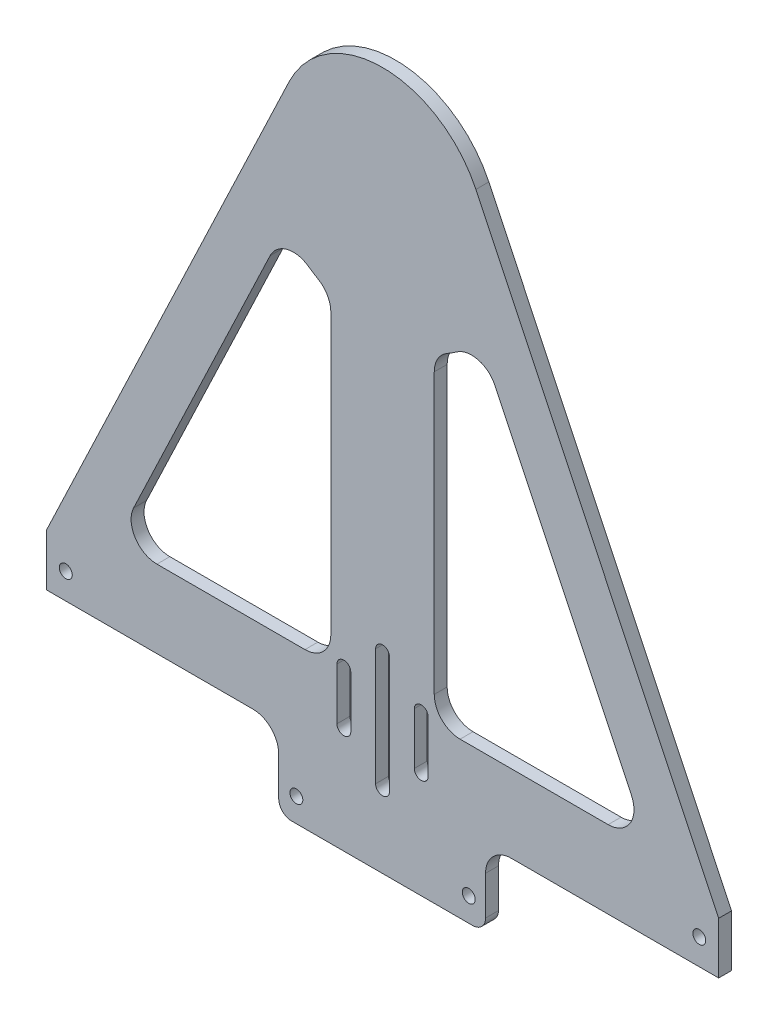
SolidWorks part; units mm, degrees
material "Titanium Ti-8Al-1Mo-1V"
ref_plane "Front Plane" through (0, 0, 0) normal (0, 0, 1) x (1, 0, 0)
ref_plane "Top Plane" through (0, 0, 0) normal (0, 1, 0) x (1, 0, 0)
ref_plane "Right Plane" through (0, 0, 0) normal (1, 0, 0) x (0, 0, -1)
sketch "Sketch1" plane through (0, 0, 0) normal (0, 0, 1) x (1, 0, 0)
  line L0 (0, -58.42) -> (0, 58.42) construction
  line L2 (-82.55, 55.7897) -> (-82.55, -52.07)
  line L3 (-76.2, -58.42) -> (76.2, -58.42)
  line L4 (82.55, 55.7897) -> (82.55, -52.07)
  line L5 (-82.55, 58.42) -> (82.55, -58.42) construction
  line L6 (-82.55, -58.42) -> (82.55, 58.42) construction
  line L7 (-80.6901, 60.2799) -> (-75.4296, 65.5404)
  line L8 (-70.9395, 67.4003) -> (-50.8, 67.4003)
  line L9 (-46.3099, 65.5404) -> (-41.0494, 60.2799)
  line L10 (46.3099, 65.5404) -> (41.0494, 60.2799)
  line L11 (70.9395, 67.4003) -> (50.8, 67.4003)
  line L12 (80.6901, 60.2799) -> (75.4296, 65.5404)
  line L13 (-73.5697, 67.4003) -> (-82.55, 67.4003) construction
  line L14 (-82.55, 67.4003) -> (-82.55, 58.42) construction
  line L15 (-36.5592, 58.42) -> (0, 58.42)
  line L16 (0, 58.42) -> (36.5592, 58.42)
  circle A0 centre (-77.7875, -35.052) radius 1.5875
  circle A1 centre (-77.7875, -11.684) radius 1.5875
  circle A2 centre (-77.7875, 11.684) radius 1.5875
  circle A3 centre (-77.7875, 35.052) radius 1.5875
  circle A4 centre (77.7875, 35.052) radius 1.5875
  circle A5 centre (77.7875, 11.684) radius 1.5875
  circle A6 centre (77.7875, -11.684) radius 1.5875
  circle A7 centre (77.7875, -35.052) radius 1.5875
  arc A8 (82.55, 55.7897) -> (80.6901, 60.2799) centre (76.2, 55.7897) ccw
  arc A9 (75.4296, 65.5404) -> (70.9395, 67.4003) centre (70.9395, 61.0503) ccw
  arc A10 (46.3099, 65.5404) -> (50.8, 67.4003) centre (50.8, 61.0503) cw
  arc A11 (41.0494, 60.2799) -> (36.5592, 58.42) centre (36.5592, 64.77) cw
  arc A12 (-36.5592, 58.42) -> (-41.0494, 60.2799) centre (-36.5592, 64.77) cw
  arc A13 (-46.3099, 65.5404) -> (-50.8, 67.4003) centre (-50.8, 61.0503) ccw
  arc A14 (-70.9395, 67.4003) -> (-75.4296, 65.5404) centre (-70.9395, 61.0503) ccw
  arc A15 (-82.55, 55.7897) -> (-80.6901, 60.2799) centre (-76.2, 55.7897) cw
  arc A16 (76.2, -58.42) -> (82.55, -52.07) centre (76.2, -52.07) ccw
  arc A17 (-76.2, -58.42) -> (-82.55, -52.07) centre (-76.2, -52.07) cw
  circle A18 centre (-70.9395, 61.0503) radius 1.5875
  circle A19 centre (-50.8, 61.0503) radius 1.5875
  circle A20 centre (50.8, 61.0503) radius 1.5875
  circle A21 centre (70.9395, 61.0503) radius 1.5875
  point P0 (0, 0)
  point P36 (73.5697, 67.4003)
  point P39 (48.1697, 67.4003)
  point P42 (39.1895, 58.42)
  point P45 (-39.1895, 58.42)
  point P48 (-48.1697, 67.4003)
  dimension "D3" = 3.175
  dimension "D11" = 6.35
  dimension "D12" = 6.35
  dimension "D13" = 3.175
  dimension "D14" = 3.175
  dimension "D1" = 165.1
  dimension "D2" = 116.84
  dimension "D4" = 23.368
  dimension "D5" = 4.7625
  dimension "D7" = 46.736
  dimension "D8" = 12.7
  dimension "D9" = 135
  dimension "D10" = 25.4
  dimension "D6" = 4
extrude "Boss-Extrude1" [suppressed] add sketch "Sketch1" along normal blind 1.5
sketch "Sketch2" [suppressed] plane through (0, 0, 1.5) normal (0, 0, 1) x (1, 0, 0)
  line L0 (0, -45.72) -> (0, 6.3634) construction
  line L1 (0, -58.42) -> (0, 63.5) construction
  line L3 (-82.55, 1.8599) -> (82.55, 1.8599) construction
  line L4 (-82.55, 55.7897) -> (-82.55, -52.07) construction
  line L5 (82.55, -52.07) -> (82.55, 55.7897) construction
  line L7 (-76.2, -58.42) -> (76.2, -58.42) construction
  circle A0 centre (0, -45.72) radius 1.9062
  circle A1 centre (0, 6.3634) radius 1.9062
  dimension "D2" = 3.8125
  dimension "D3" = 3.8125
  dimension "D1" = 52.0834
  dimension "D4" = 12.7
extrude "Cut-Extrude1" [suppressed] cut sketch "Sketch2" against normal through all
sketch "Sketch3" [suppressed] plane through (0, 0, 1.5) normal (0, 0, 1) x (1, 0, 0)
  line L0 (0, 50.8) -> (0, 30.8) construction
  line L1 (-10, 40.8) -> (10, 40.8) construction
  line L2 (-10, 40.8) -> (0, 50.8) construction
  line L3 (0, 50.8) -> (10, 40.8) construction
  line L4 (10, 40.8) -> (0, 30.8) construction
  line L5 (0, 30.8) -> (-10, 40.8) construction
  line L6 (0, 63.5) -> (0, -58.42) construction
  line L8 (-76.2, -58.42) -> (76.2, -58.42) construction
  circle A0 centre (0, 50.8) radius 1.8669
  circle A1 centre (-10, 40.8) radius 1.8669
  circle A2 centre (0, 30.8) radius 1.8669
  circle A3 centre (10, 40.8) radius 1.8669
  dimension "D1" = 3.7338
  dimension "D2" = 12.7
extrude "Cut-Extrude2" [suppressed] cut sketch "Sketch3" against normal through all
sketch "Sketch4" [suppressed] plane through (0, 0, 1.5) normal (0, 0, 1) x (1, 0, 0)
  line L0 (0, 58.42) -> (0, -58.42) construction
  line L1 (36.5592, 58.42) -> (-36.5592, 58.42) construction
  line L2 (-76.2, -58.42) -> (76.2, -58.42) construction
  line L5 (0, 33.045) -> (0, 52.045) construction
  line L6 (-9.5, 42.545) -> (9.5, 42.545) construction
  circle A14 centre (0, 42.545) radius 8 construction
  circle A15 centre (0, 42.545) radius 9.5 construction
  circle A16 centre (0, 50.545) radius 1.5
  circle A17 centre (0, 34.545) radius 1.5
  circle A18 centre (-9.5, 42.545) radius 1.5
  circle A19 centre (9.5, 42.545) radius 1.5
  dimension "D1" = 15.875
  dimension "D3" = 16
  dimension "D4" = 19
  dimension "D5" = 3
  dimension "D6" = 3
  dimension "D7" = 3
  dimension "D8" = 3
extrude "Cut-Extrude3" [suppressed] cut sketch "Sketch4" against normal through all
sketch "Sketch5" plane through (0, 0, 0) normal (0, 0, 1) x (1, 0, 0)
  line L0 (0, 58.42) -> (0, 26.67) construction
  line L1 (-82.55, 58.42) -> (82.55, 58.42) construction
  line L2 (-82.55, 58.42) -> (-82.55, 45.72)
  line L4 (82.55, 58.42) -> (82.55, 45.72)
  line L5 (82.55, 58.42) -> (22.9335, 183.6386)
  line L8 (77.7875, 45.72) -> (77.7875, 58.42) construction
  line L11 (0, -48.26) -> (0, -46.3538) construction
  line L12 (0, 58.42) -> (0, 172.72) construction
  line L14 (-82.55, 45.72) -> (-31.849, 45.72)
  line L15 (-22.324, 26.67) -> (22.126, 26.67)
  line L16 (-25.499, 29.845) -> (-25.499, 39.37)
  line L17 (25.301, 29.845) -> (25.301, 39.37)
  line L18 (31.651, 45.72) -> (82.55, 45.72)
  line L19 (-82.55, 58.42) -> (-22.9335, 183.6386)
  line L20 (-77.7875, 45.72) -> (-77.7875, 58.42) construction
  line L23 (0, -0.6801) -> (0, 0) construction
  line L24 (0, 26.67) -> (0, 58.42) construction
  line L26 (0, 58.42) -> (-82.55, 58.42) construction
  line L27 (-61.138, 73.8497) -> (-27.6156, 144.2603)
  line L28 (0, -48.26) -> (0, -46.3538) construction
  line L37 (68.4841, 58.42) -> (11.4667, 178.1793) construction
  line L38 (31.651, 58.42) -> (68.4841, 58.42) construction
  line L39 (12.601, 39.37) -> (12.601, 39.37) construction
  line L40 (-12.799, 39.37) -> (12.601, 39.37) construction
  line L41 (-12.799, 39.37) -> (-12.799, 39.37) construction
  line L42 (-68.4841, 58.42) -> (-31.849, 58.42) construction
  line L43 (-12.7, 71.12) -> (-12.7, 139.7244)
  line L44 (-68.4841, 58.42) -> (-11.4667, 178.1793) construction
  line L45 (68.4841, 58.42) -> (68.4841, 58.42) construction
  line L46 (-55.4047, 64.77) -> (-19.05, 64.77)
  line L47 (-12.7, 58.42) -> (-12.7, 172.72) construction
  line L48 (19.05, 64.77) -> (55.4047, 64.77) construction
  line L49 (-82.55, 64.77) -> (82.55, 64.77) construction
  line L50 (-68.4841, 58.42) -> (-68.4841, 58.42) construction
  line L51 (61.138, 73.8497) -> (27.6156, 144.2603)
  line L52 (55.4047, 64.77) -> (19.05, 64.77)
  line L53 (12.7, 71.12) -> (12.7, 139.7244)
  line L54 (-11.2, 52.9151) -> (-11.2, 65.6151)
  line L55 (-7.8, 52.9151) -> (-7.8, 65.6151)
  line L56 (-1.7, 44.9151) -> (-1.7, 73.6151)
  line L57 (1.7, 44.9151) -> (1.7, 73.6151)
  line L58 (7.8, 52.9151) -> (7.8, 65.6151)
  line L59 (11.2, 52.9151) -> (11.2, 65.6151)
  arc A12 (-25.499, 39.37) -> (-31.849, 45.72) centre (-31.849, 39.37) ccw
  arc A13 (25.301, 39.37) -> (31.651, 45.72) centre (31.651, 39.37) cw
  arc A14 (25.301, 29.845) -> (22.126, 26.67) centre (22.126, 29.845) cw
  arc A15 (-25.499, 29.845) -> (-22.324, 26.67) centre (-22.324, 29.845) ccw
  circle A16 centre (-77.7875, 52.07) radius 1.5875
  circle A17 centre (77.7875, 52.07) radius 1.5875
  arc A18 (22.9335, 183.6386) -> (-22.9335, 183.6386) centre (0, 172.72) ccw
  circle A19 centre (0, 172.72) radius 25.4 construction
  arc A25 (11.4667, 178.1793) -> (-11.4667, 178.1793) centre (0, 172.72) ccw construction
  arc A26 (12.601, 39.37) -> (31.651, 58.42) centre (31.651, 39.37) cw construction
  arc A27 (-12.799, 39.37) -> (-31.849, 58.42) centre (-31.849, 39.37) ccw construction
  arc A28 (12.601, 39.37) -> (12.601, 39.37) centre (12.601, 39.37) cw construction
  arc A29 (-12.799, 39.37) -> (-12.799, 39.37) centre (-12.799, 39.37) ccw construction
  arc A30 (-18.2352, 146.7288) -> (-15.875, 145.2237) centre (0, 172.72) ccw
  arc A31 (-18.2352, 146.7288) -> (-27.6156, 144.2603) centre (-21.8822, 141.5306) ccw
  circle A32 centre (0, 172.72) radius 31.75 construction
  arc A33 (-15.875, 145.2237) -> (-12.7, 139.7244) centre (-19.05, 139.7244) cw
  arc A34 (-19.05, 64.77) -> (-12.7, 71.12) centre (-19.05, 71.12) ccw
  arc A35 (-55.4047, 64.77) -> (-61.138, 73.8497) centre (-55.4047, 71.12) cw
  arc A36 (15.875, 145.2237) -> (12.7, 139.7244) centre (19.05, 139.7244) ccw
  arc A37 (18.2352, 146.7288) -> (15.875, 145.2237) centre (0, 172.72) cw
  arc A38 (18.2352, 146.7288) -> (27.6156, 144.2603) centre (21.8822, 141.5306) cw
  arc A39 (55.4047, 64.77) -> (61.138, 73.8497) centre (55.4047, 71.12) ccw
  arc A40 (19.05, 64.77) -> (12.7, 71.12) centre (19.05, 71.12) cw
  circle A57 centre (0, 52.9151) radius 8 construction
  circle A58 centre (0, 52.9151) radius 9.5 construction
  arc A59 (7.8, 52.9151) -> (11.2, 52.9151) centre (9.5, 52.9151) ccw
  arc A60 (-11.2, 52.9151) -> (-7.8, 52.9151) centre (-9.5, 52.9151) ccw
  arc A62 (-1.7, 44.9151) -> (1.7, 44.9151) centre (0, 44.9151) ccw
  arc A63 (-7.8, 65.6151) -> (-11.2, 65.6151) centre (-9.5, 65.6151) ccw
  arc A64 (11.2, 65.6151) -> (7.8, 65.6151) centre (9.5, 65.6151) ccw
  arc A65 (1.7, 73.6151) -> (-1.7, 73.6151) centre (0, 73.6151) ccw
  circle A66 centre (-21.1667, 32.5034) radius 1.5875
  circle A67 centre (21.1667, 32.5034) radius 1.5875
  point P0 (0, 0)
  point P52 (25.301, 45.72)
  point P55 (25.301, 26.67)
  point P58 (-25.499, 26.67)
  point P68 (30.3627, 182.0028)
  dimension "D17" = 6.35
  dimension "D18" = 6.35
  dimension "D19" = 3.175
  dimension "D20" = 3.175
  dimension "D21" = 3.175
  dimension "D4" = 50.8
  dimension "D24" = 6.35
  dimension "D25" = 16
  dimension "D26" = 19
  dimension "D27" = 3.4
  dimension "D28" = 3.4
  dimension "D30" = 3.4
  dimension "D31" = 3.4
  dimension "D32" = 3.4
  dimension "D35" = 3.4
  dimension "D36" = 3.175
  dimension "D14" = 12.7
  dimension "D15" = 50.8
  dimension "D16" = 19.05
  dimension "D22" = 6.35
  dimension "D3" = 114.3
  dimension "D33" = 12.7
  dimension "D34" = 12.7
  dimension "D8" = 25.9166
  dimension "D6" = 6.35
  dimension "D7" = 12.7
  dimension "D23" = 6.35
extrude "Boss-Extrude2" add sketch "Sketch5" along normal blind 3.175
equation "\"Top Plate Width\" = 4.5in"
equation "\"Plate Width\" = 3.5in"
equation "\"Plate Thickness\" = 0.375in"
equation "\"Num holes\" = 4"
equation "\"Plate Height\" = 1.25in"
equation "\"Plate Clearance Hole Diameter\" = 0.125in"
equation "\"D3@Sketch1\"=\"Plate Clearance Hole Diameter\""
equation "\"Hole Spacing\"= \"Plate Width\" / ( \"Num holes\" + 1 )"
equation "\"Plate Tap Hole Diameter\" = 0.116in"
equation "\"Bottom Plate Length\" = 6.5in"
equation "\"D21@Sketch5\"=\"Plate Clearance Hole Diameter\""
equation "\"Number Eight Clearance Size\" = 0.177in"
equation "\"Back Brace Height\" = 1.1962912in"
equation "\"Titanium Offset Length\" = 4.5in"
equation "\"Titanium Head Radius\" = 2in"
equation "\"D3@Sketch5\"=\"Titanium Offset Length\""
equation "\"D4@Sketch5\"=\"Titanium Head Radius\""
equation "\"Titanium Plate Border Thickness\" = 0.5in"
equation "\"D5@Sketch5\"=\"Titanium Plate Border Thickness\""
equation "\"D6@Sketch5\"=\"Titanium Plate Border Thickness\" / 2"
equation "\"D23@Sketch5\"=\"Titanium Plate Border Thickness\"/2"
equation "\"slot_hole_length\"=0.75"
